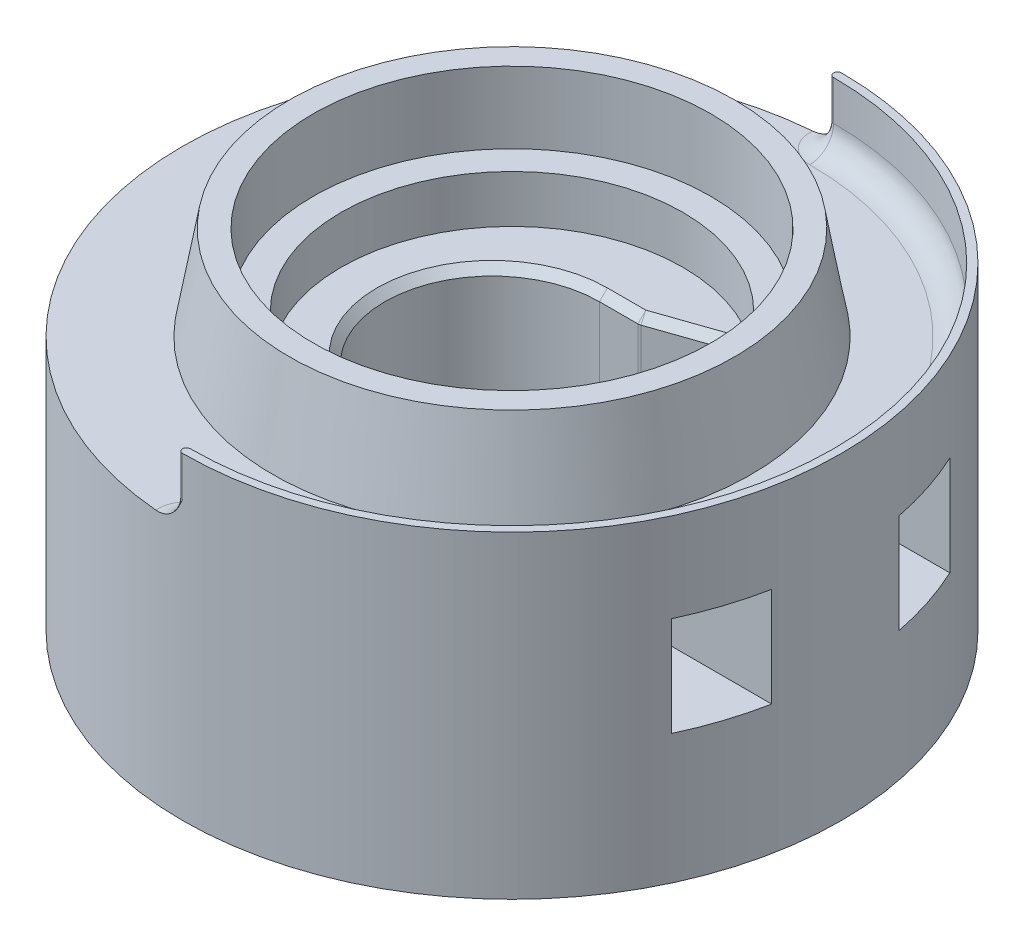
SolidWorks part; units mm, degrees
ref_plane "Front Plane" through (0, 0, 0) normal (0, 0, 1) x (1, 0, 0)
ref_plane "Top Plane" through (0, 0, 0) normal (0, 1, 0) x (1, 0, 0)
ref_plane "Right Plane" through (0, 0, 0) normal (1, 0, 0) x (0, 0, -1)
sketch "Sketch2" plane through (0, 0, 0) normal (0, 0, 1) x (1, 0, 0)
  line L4 (-21.5, 28.8) -> (-21.5, 34.7865)
  line L5 (-21.5, 34.7865) -> (-25, 34.7865)
  line L6 (-25, 34.7865) -> (-25, 43.7865)
  line L7 (-25, 43.7865) -> (-28, 43.7865)
  line L8 (-28, 43.7865) -> (-30.0783, 32)
  line L14 (-41.45, 32) -> (-41.45, 0)
  line L15 (-41.45, 0) -> (0, 0)
  line L16 (-21.5, 28.8) -> (0, 28.8)
  line L18 (0, 0) -> (0, 28.8)
  line L20 (-41.45, 32) -> (-30.0783, 32)
  point P1 (-33.0642, 34.7865)
  dimension "D1" = 41.45
  dimension "D2" = 25
  dimension "D3" = 21.5
  dimension "D4" = 9
  dimension "D5" = 28.8
  dimension "D6" = 3
  dimension "D7" = 100
  dimension "D8" = 32
revolve "Revolve1" add sketch "Sketch2" angle 360 about L18
sketch "Sketch3" plane through (0, 28.8, 0) normal (0, 1, 0) x (1, 0, 0)
  line L0 (-2.5, 0) -> (2.5, 0) construction
  line L1 (-2.5, 13.5) -> (2.5, 13.5)
  line L2 (-2.5, -13.5) -> (2.5, -13.5)
  line L4 (27.2, 8) -> (17.6079, 8)
  line L5 (27.2, 8) -> (27.2, -8)
  line L6 (27.2, -8) -> (17.6079, -8)
  line L8 (27.2, 8) -> (13.3743, -8) construction
  line L9 (27.2, -8) -> (13.3743, 8) construction
  arc A0 (-2.5, 13.5) -> (-2.5, -13.5) centre (-2.5, 0) ccw
  arc A1 (2.5, -13.5) -> (11.179, -10.3404) centre (2.5, 0) ccw
  arc A2 (11.179, 10.3404) -> (2.5, 13.5) centre (2.5, 0) ccw
  arc A3 (17.6079, -8) -> (11.179, -10.3404) centre (17.6079, -18) ccw
  arc A4 (17.6079, 8) -> (11.179, 10.3404) centre (17.6079, 18) cw
  point P2 (0, 0)
  point P8 (-16, 0)
  point P10 (20.2871, 0)
  dimension "D2" = 10
  dimension "D1" = 27
  dimension "D3" = 43.2
  dimension "D4" = 16
extrude "Cut-Extrude1" cut sketch "Sketch3" against normal through all
sketch "Sketch4" plane through (0, 28.8, 0) normal (0, 1, 0) x (1, 0, 0)
  line L0 (14.75, 13.35) -> (14.75, -13.35) construction
  line L1 (18.9, 13.35) -> (18.9, -13.35)
  line L2 (10.6, 13.35) -> (10.6, -13.35)
  line L3 (27.2, -8) -> (27.2, 8) construction
  line L4 (2.5, 13.5) -> (13.3921, 17.2716)
  line L5 (2.5, 13.5) -> (2.5, -13.5)
  line L6 (2.5, -13.5) -> (13.3921, -17.2716)
  arc A0 (18.9, 13.35) -> (10.6, 13.35) centre (14.75, 13.35) ccw
  arc A1 (10.6, -13.35) -> (18.9, -13.35) centre (14.75, -13.35) ccw
  point P2 (14.75, 0)
  point P15 (14.75, -17.5)
  point P19 (14.75, 17.5)
  dimension "D3" = 4.15
  dimension "D1" = 8.3
  dimension "D2" = 35
extrude "Cut-Extrude2" cut sketch "Sketch4" against normal blind 12.5
sketch "Sketch5" plane through (0, 16.3, 0) normal (0, 1, 0) x (1, 0, 0)
  point P1 (18.9, 8)
  point P2 (18.9, -8)
ref_plane "Plane1" through (14.75, 0, 0) normal (1, 0, 0) x (0, 0, -1)
sketch "Sketch6" plane through (14.75, 0, 0) normal (1, 0, 0) x (0, 0, -1)
  line L0 (10.3404, 16.3) -> (8, 16.3) construction
  line L1 (8, 16.3) -> (17.5, 16.3)
  line L2 (8, 16.3) -> (8, 28.8)
  line L3 (8, 28.8) -> (17.5, 28.8)
  line L4 (17.5, 16.3) -> (17.5, 28.8)
  line L5 (17.5, 28.8) -> (13.35, 28.8) construction
  line L6 (0, 55) -> (0, -55) construction
  line L7 (-8, 28.8) -> (-17.5, 28.8)
  line L8 (-17.5, 16.3) -> (-17.5, 28.8)
  line L9 (-8, 16.3) -> (-17.5, 16.3)
  line L10 (-8, 16.3) -> (-8, 28.8)
  point P8 (0, 0)
  point P9 (14.6893, 28.8)
  point P10 (17.5, 28.8)
  point P12 (6.4903, 16.3)
  point P19 (8, 16.3)
extrude "Cut-Extrude3" cut sketch "Sketch6" along normal through all
sketch "Sketch7" plane through (0, 16.3, 0) normal (0, 1, 0) x (1, 0, 0)
  line L0 (-55, 0) -> (55, 0) construction
  circle A0 centre (15.55, 13.1) radius 2.25
  circle A2 centre (15.55, -13.1) radius 2.25
  dimension "D2" = 4.5
  dimension "D3" = 15.55
  dimension "D4" = 13.1
extrude "Cut-Extrude4" cut sketch "Sketch7" against normal through all
sketch "Sketch8" plane through (0, 0, 0) normal (0, -1, 0) x (1, 0, 0)
  line L0 (2.5, 13.5) -> (14.4418, 16.9434)
  line L1 (19.55, 13.1) -> (19.55, 8)
  line L2 (17.6079, 8) -> (27.2, 8) construction
  line L3 (19.55, 8) -> (2.5, 8)
  line L4 (2.5, 8) -> (2.5, 13.5)
  line L5 (55, 0) -> (-55, 0) construction
  line L6 (19.55, -13.1) -> (19.55, -8)
  line L7 (19.55, -8) -> (2.5, -8)
  line L8 (2.5, -8) -> (2.5, -13.5)
  line L9 (2.5, -13.5) -> (14.4418, -16.9434)
  arc A0 (19.55, 13.1) -> (14.4418, 16.9434) centre (15.55, 13.1) ccw
  arc A2 (19.55, -13.1) -> (14.4418, -16.9434) centre (15.55, -13.1) cw
  circle A3 centre (15.55, 13.1) radius 2.25 construction
  dimension "D1" = 4
extrude "Cut-Extrude5" cut sketch "Sketch8" against normal blind 5
fillet "Fillet1" radius 1 6 edges at (2.5, 2.5, -13.5) (2.5, 22.55, -13.5) (2.5, 2.5, 13.5) (2.5, 22.55, 13.5) (19.55, 2.5, -8) (19.55, 2.5, 8)
sketch "Sketch9" plane through (0, 32, 0) normal (0, 1, 0) x (1, 0, 0)
  arc A0 (0, 40.95) -> (0, -40.95) centre (0, 0) cw construction
  arc A1 (0, -41.45) -> (0, 41.45) centre (0, 0) ccw
  arc A2 (0, -40.45) -> (0, 40.45) centre (0, 0) ccw
  arc A3 (0, -40.45) -> (0, -41.45) centre (0, -40.95) ccw
  arc A4 (0, 41.45) -> (0, 40.45) centre (0, 40.95) ccw
  point P4 (40.95, 0)
  dimension "D1" = 40.95
  dimension "D2" = 1
extrude "Boss-Extrude1" add sketch "Sketch9" along normal blind 8
chamfer "Chamfer1" distance 1 angle 45 7 edges at (7.8244, 28.8, -15.3437) (7.8244, 28.8, 15.3437) (2.4977, 28.8, -13.5139) (2.4977, 28.8, 13.5139) (-0.0841, 28.8, -13.5) (-0.0841, 28.8, 13.5) (-16, 28.8, 0)
fillet "Fillet2" radius 3 3 edges at (-0.5, 32, -40.95) (-0.5, 32, 40.95) (40.45, 32, 0)
